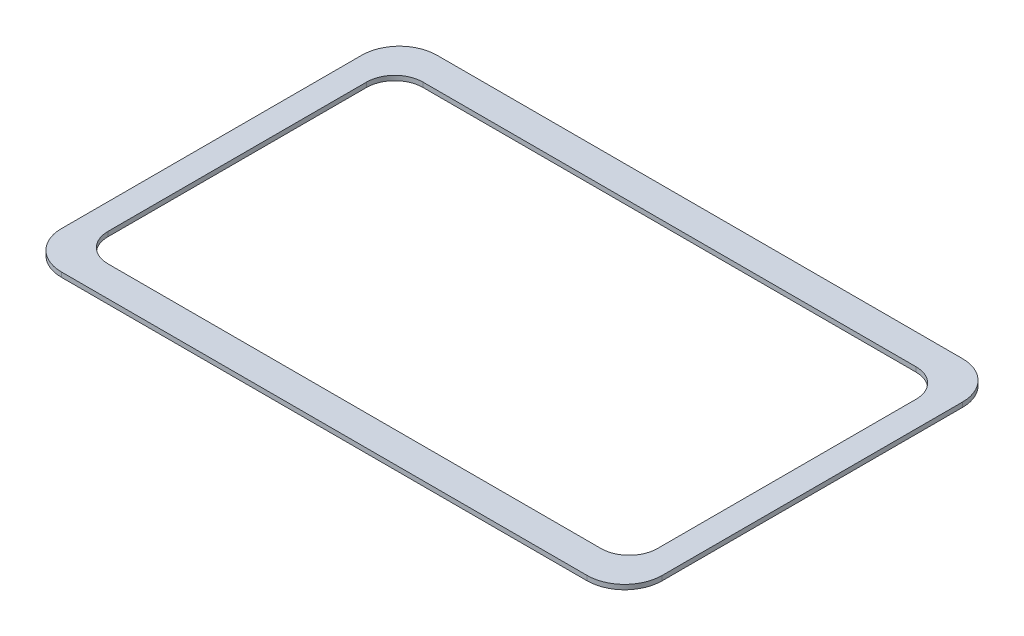
SolidWorks part; units mm, degrees
ref_plane "Front Plane" through (0, 0, 0) normal (0, 0, 1) x (1, 0, 0)
ref_plane "Top Plane" through (0, 0, 0) normal (0, 1, 0) x (1, 0, 0)
ref_plane "Right Plane" through (0, 0, 0) normal (1, 0, 0) x (0, 0, -1)
sketch "Sketch2" plane through (0, 49.0346, 0) normal (0, 1, 0) x (1, 0, 0)
  line L23 (74.7125, 86.6466) -> (-103.0875, 86.6466)
  line L24 (87.4125, -27.6534) -> (87.4125, 73.9466)
  line L25 (-97.5843, -30.1159) -> (69.2092, -30.1159)
  line L26 (-97.5843, -30.1159) -> (69.2092, -30.1159)
  line L32 (-103.0875, -40.3534) -> (74.7125, -40.3534) construction
  line L33 (-115.7875, 73.9466) -> (-115.7875, -27.6534) construction
  line L34 (-103.0875, -40.3534) -> (74.7125, -40.3534)
  line L35 (-115.7875, 73.9466) -> (-115.7875, -27.6534)
  line L66 (69.2092, 76.4092) -> (-97.5843, 76.4092)
  line L69 (69.2092, 76.4092) -> (-97.5843, 76.4092)
  line L104 (78.733, -20.5922) -> (78.733, 66.8854)
  line L107 (78.733, -20.5922) -> (78.733, 66.8854)
  line L119 (-107.108, 66.8854) -> (-107.108, 23.1466)
  line L120 (-107.108, 66.8854) -> (-107.108, 23.1466)
  line L121 (-107.108, 23.1466) -> (-107.108, -20.5922)
  line L122 (-107.108, 23.1466) -> (-107.108, -20.5922)
  arc A2 (87.4125, 73.9466) -> (74.7125, 86.6466) centre (74.7125, 73.9466) ccw
  arc A17 (-103.0875, 86.6466) -> (-115.7875, 73.9466) centre (-103.0875, 73.9466) ccw
  arc A21 (-107.108, -20.5922) -> (-97.5843, -30.1159) centre (-97.5843, -20.5922) ccw
  arc A25 (-107.108, -20.5922) -> (-97.5843, -30.1159) centre (-97.5843, -20.5922) ccw
  arc A29 (74.7125, -40.3534) -> (87.4125, -27.6534) centre (74.7125, -27.6534) ccw construction
  arc A30 (-115.7875, -27.6534) -> (-103.0875, -40.3534) centre (-103.0875, -27.6534) ccw construction
  arc A31 (74.7125, -40.3534) -> (87.4125, -27.6534) centre (74.7125, -27.6534) ccw
  arc A32 (-115.7875, -27.6534) -> (-103.0875, -40.3534) centre (-103.0875, -27.6534) ccw
  arc A49 (69.2092, -30.1159) -> (78.733, -20.5922) centre (69.2092, -20.5922) ccw
  arc A50 (69.2092, -30.1159) -> (78.733, -20.5922) centre (69.2092, -20.5922) ccw
  arc A51 (78.733, 66.8854) -> (69.2092, 76.4092) centre (69.2092, 66.8854) ccw
  arc A52 (78.733, 66.8854) -> (69.2092, 76.4092) centre (69.2092, 66.8854) ccw
  arc A53 (-97.5843, 76.4092) -> (-107.108, 66.8854) centre (-97.5843, 66.8854) ccw
  arc A54 (-97.5843, 76.4092) -> (-107.108, 66.8854) centre (-97.5843, 66.8854) ccw
  dimension "D1" = 1.5875
extrude "MainBody" add sketch "Sketch2" along normal blind 1.5875
equation "\"ClampDepth\"= 3 / 8in"
equation "\"D1@Sketch2\"=0.0625"
